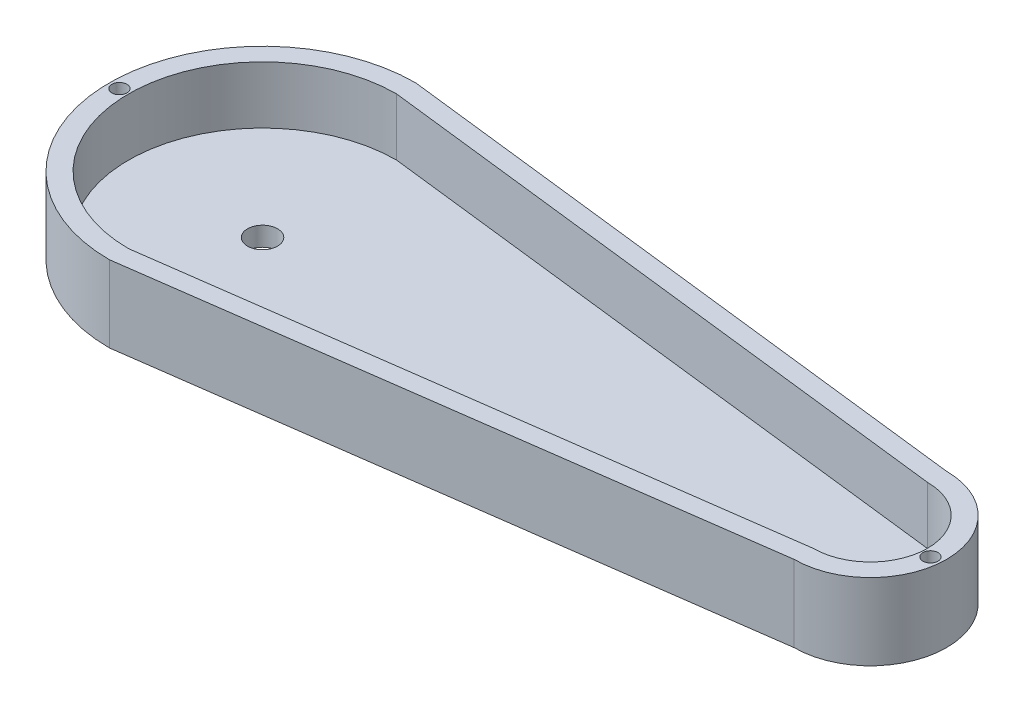
SolidWorks part; units mm, degrees
ref_plane "Front Plane" through (0, 0, 0) normal (0, 0, 1) x (1, 0, 0)
ref_plane "Top Plane" through (0, 0, 0) normal (0, 1, 0) x (1, 0, 0)
ref_plane "Right Plane" through (0, 0, 0) normal (1, 0, 0) x (0, 0, -1)
sketch "Sketch1" plane through (0, 0, 0) normal (0, 1, 0) x (1, 0, 0)
  line L0 (0, 50.8924) -> (200.0001, 27.3028)
  line L1 (200.0001, -23.3712) -> (0, -50.8924)
  arc A0 (0, -50.8924) -> (0, 50.8924) centre (0, 0) cw
  arc A1 (200.0001, -23.3712) -> (200.0001, 27.3028) centre (200.0001, 1.9658) ccw
extrude "Boss-Extrude1" add sketch "Sketch1" along normal blind 25.4 contours L1 A0 L0 A1
sketch "Sketch2" plane through (0, 25.4, 0) normal (0, 1, 0) x (1, 0, 0)
  line L0 (0, 44.5318) -> (200.0001, 20.9585)
  line L1 (200.0001, -17.0269) -> (0, -44.5318)
  arc A0 (0, -44.5318) -> (0, 44.5318) centre (0, 0) cw
  arc A1 (200.0001, -17.0269) -> (200.0001, 20.9585) centre (200.0001, 1.9658) ccw
  circle A2 centre (-47.498, 0) radius 2.54
  dimension "D1" = 5.08
extrude "Cut-Extrude1" cut sketch "Sketch2" against normal blind 19.05 contours L1 A0 L0 A1
sketch "Sketch3" plane through (0, 25.4, 0) normal (0, 1, 0) x (1, 0, 0)
  circle A0 centre (-47.5691, 0) radius 2.5
  arc A1 (0, 44.5318) -> (0, -44.5318) centre (0, 0) ccw construction
  arc A2 (0, 50.8924) -> (0, -50.8924) centre (0, 0) ccw construction
  circle A3 centre (221.9261, 0) radius 2.5
  arc A4 (200.0001, -23.3712) -> (200.0001, 27.3028) centre (200.0001, 1.9658) ccw construction
  arc A5 (200.0001, -17.0269) -> (200.0001, 20.9585) centre (200.0001, 1.9658) ccw construction
  point P6 (-44.5318, 0)
  point P11 (-50.8924, 0)
  point P15 (225.3371, 1.9658)
  point P20 (218.9928, 1.9658)
  dimension "D1" = 5
  dimension "D4" = 5
  dimension "D2" = 3.0372
  dimension "D3" = 3.3233
  dimension "D5" = 3.4109
  dimension "D6" = 2.9334
extrude "Cut-Extrude2" cut sketch "Sketch3" against normal blind 25.4
sketch "Sketch5" plane through (0, 6.35, 0) normal (0, 1, 0) x (1, 0, 0)
  circle A0 centre (0, 0) radius 5
sketch "Sketch6" plane through (0, 6.35, 0) normal (0, 1, 0) x (1, 0, 0)
  circle A0 centre (200.0001, 0) radius 5
extrude "Cut-Extrude3" cut sketch "Sketch6" against normal blind 6.35
extrude "Cut-Extrude4" cut sketch "Sketch5" against normal blind 6.35
